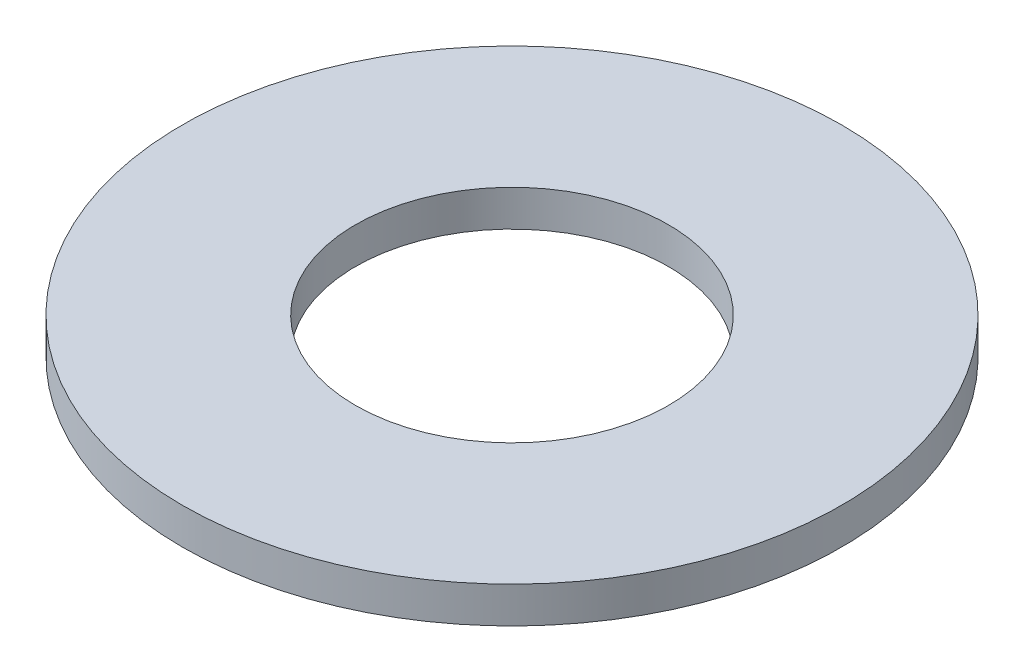
SolidWorks part; units mm, degrees
ref_plane "Front Plane" through (0, 0, 0) normal (0, 0, 1) x (1, 0, 0)
ref_plane "Top Plane" through (0, 0, 0) normal (0, 1, 0) x (1, 0, 0)
ref_plane "Right Plane" through (0, 0, 0) normal (1, 0, 0) x (0, 0, -1)
sketch "Sketch1" plane through (0, 0, 0) normal (0, 1, 0) x (1, 0, 0)
  circle A0 centre (0, 0) radius 100
  dimension "FLANGE_OD" = 200
extrude "Boss-Extrude1" add sketch "Sketch1" along normal blind 11
sketch "Sketch2" plane through (0, 0, 0) normal (0, 1, 0) x (1, 0, 0)
  circle A0 centre (0, 0) radius 47.5
  dimension "BORE_D" = 95
extrude "Cut-Extrude1" cut sketch "Sketch2" along normal through all
sketch "Sketch3" plane through (0, 11, 0) normal (0, 1, 0) x (1, 0, 0)
  circle A0 centre (0, 0) radius 39.8194 construction
  circle A1 centre (-39.8194, 0) radius 2.2413
  dimension "BOLT_D" = 4.4826
  dimension "BOLT_PCD" = 79.6388
extrude "Cut-Extrude2" cut sketch "Sketch3" against normal blind 8.7015 rebuild error yes
pattern_circular "CirPattern1" count 8 over 360 rebuild error yes
